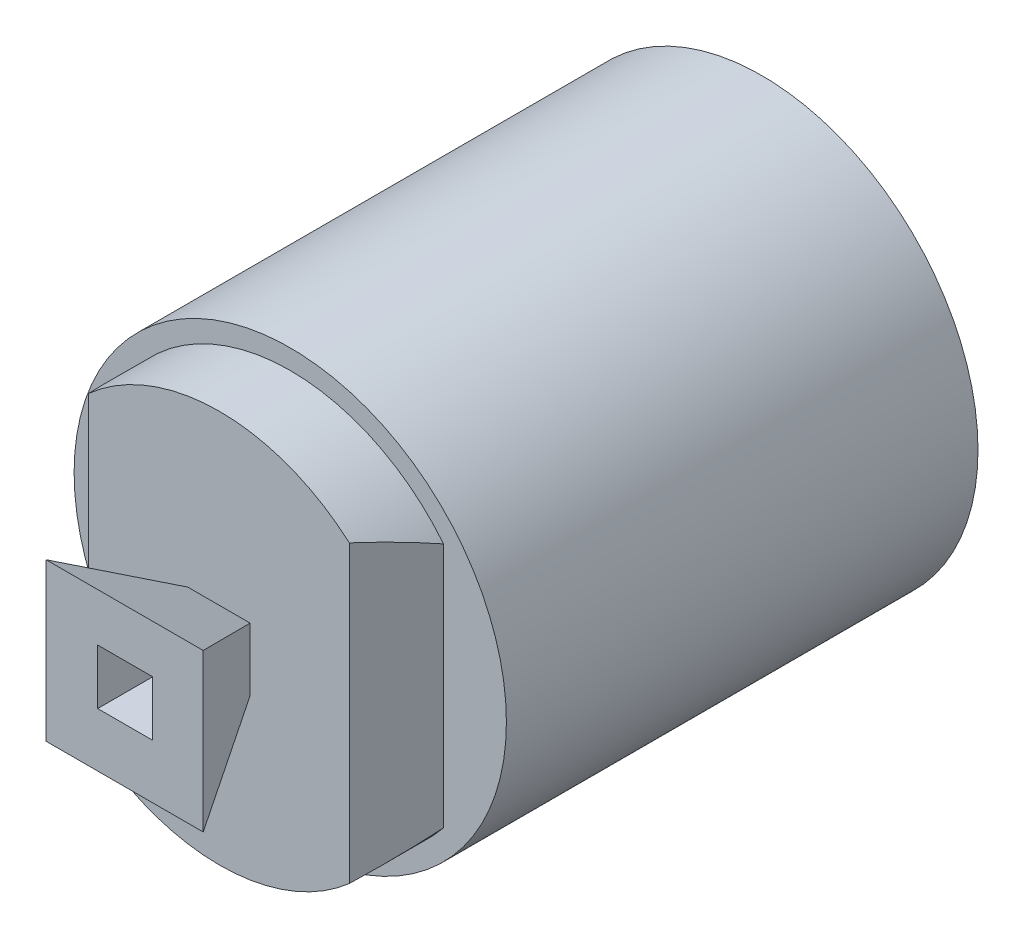
SolidWorks part; units mm, degrees
ref_plane "Plano frontal" through (0, 0, 0) normal (0, 0, 1) x (1, 0, 0)
ref_plane "Plano superior" through (0, 0, 0) normal (0, 1, 0) x (1, 0, 0)
ref_plane "Plano direito" through (0, 0, 0) normal (1, 0, 0) x (0, 0, -1)
sketch "Esboço2" plane through (0, 0, 0) normal (0, 0, 1) x (1, 0, 0)
  circle A0 centre (0, 0) radius 27.5
  dimension "D1" = 55
extrude "Ressalto-extrusão1" add sketch "Esboço2" along normal blind 60
sketch "Esboço3" plane through (0, 0, 0) normal (0, 0, 1) x (1, 0, 0)
  circle A0 centre (0, 0) radius 27
  dimension "D1" = 54
extrude "Corte-extrusão3" cut sketch "Esboço3" along normal blind 59 and the other way blind 2
sketch "Esboço4" plane through (0, 0, 0) normal (0, 0, 1) x (1, 0, 0)
  circle A0 centre (0, 0) radius 25
  point P0 (0, 0)
  dimension "D1" = 50
extrude "Ressalto-extrusão10" add sketch "Esboço4" along normal blind 69
sketch "Esboço6" plane through (0, 0, 0) normal (0, 1, 0) x (1, 0, 0)
  line L0 (-27.6679, -60) -> (-19.6679, -60)
  line L1 (-25, -60) -> (25, -60) construction
  line L2 (27.5, -60) -> (19.5, -60)
  line L3 (16.5157, -69) -> (19.5, -60)
  line L6 (-25, -69) -> (25, -69) construction
  line L9 (-16.6679, -69) -> (-19.6679, -60)
  line L10 (-27.6679, -60) -> (-27.6679, -69)
  line L11 (-27.6679, -69) -> (-16.6679, -69)
  line L12 (16.5157, -69) -> (27.5, -69)
  line L13 (27.5, -69) -> (27.5, -60)
extrude "Corte-extrusão4" cut sketch "Esboço6" against normal blind 48 and the other way blind 43
sketch "Esboço7" plane through (0, 0, 0) normal (0, 1, 0) x (1, 0, 0)
  line L0 (-4.0434, -69) -> (3.8912, -69)
  line L1 (-16.6679, -69) -> (16.5157, -69) construction
  line L3 (-10.0761, -81) -> (9.9239, -81)
  line L4 (-10.0761, -81) -> (-4.0434, -69)
  line L5 (9.9239, -81) -> (3.8912, -69)
  point P5 (-0.0761, -69)
  point P10 (-0.0761, -81)
extrude "Ressalto-extrusão11" add sketch "Esboço7" along normal blind 20 and the other way blind 20
sketch "Esboço9" plane through (0, 0, 0) normal (1, 0, 0) x (0, 0, -1)
  line L2 (-69, -18.7678) -> (-69, 18.7678) construction
  line L4 (-81, -20) -> (-81, 20) construction
  line L6 (-81, -10.3862) -> (-69, -4.3862)
  line L7 (-69, 3.6138) -> (-81, 9.6138)
  line L8 (-81, 9.6138) -> (-81, 21.387)
  line L9 (-81, 21.387) -> (-69, 21.387)
  line L10 (-69, 25) -> (-69, 18.6328) construction
  line L11 (-69, 21.387) -> (-69, 3.6138)
  line L12 (-69, -4.3862) -> (-69, -22.8068)
  line L13 (-69, -18.6328) -> (-69, -25) construction
  line L14 (-69, -22.8068) -> (-81, -22.8068)
  line L15 (-81, -22.8068) -> (-81, -10.3862)
  point P3 (-69, -0.3862)
  point P12 (-81, -0.3862)
extrude "Corte-extrusão5" cut sketch "Esboço9" against normal blind 24 and the other way blind 30
sketch "Esboço10" plane through (0, 0, 0) normal (0, 0, 1) x (1, 0, 0)
  circle A0 centre (0, 0) radius 25.8779
extrude "Corte-extrusão6" cut sketch "Esboço10" along normal blind 59
sketch "Esboço11" plane through (0, 0, 0) normal (0, 0, 1) x (1, 0, 0)
  line L1 (16, 18) -> (-16, 18)
  line L2 (16, 18) -> (16, -18)
  line L3 (16, -18) -> (-16, -18)
  line L4 (-16, 18) -> (-16, -18)
  line L5 (16, 18) -> (-16, -18) construction
  line L6 (16, -18) -> (-16, 18) construction
  point P0 (0, 0)
  dimension "D1" = 36
  dimension "D2" = 32
extrude "Corte-extrusão7" cut sketch "Esboço11" against normal blind 1 and the other way blind 68
sketch "Esboço12" plane through (0, 0, 0) normal (0, 1, 0) x (1, 0, 0)
  line L3 (-19.0697, -58.8178) -> (18.892, -58.8178)
  line L7 (-19.0697, -58.8178) -> (-15.9488, -68)
  line L8 (18.892, -58.8178) -> (15.8473, -68)
  line L9 (-15.9488, -68) -> (15.8473, -68)
  point P20 (-0.0507, -68)
extrude "Corte-extrusão10" cut sketch "Esboço12" against normal blind 15 and the other way blind 15
sketch "Esboço13" plane through (0, 0, 0) normal (0, 0, 1) x (1, 0, 0)
  line L1 (-3.5, 3.5) -> (3.5, 3.5)
  line L2 (-3.5, 3.5) -> (-3.5, -3.5)
  line L3 (-3.5, -3.5) -> (3.5, -3.5)
  line L4 (3.5, 3.5) -> (3.5, -3.5)
  line L5 (-3.5, 3.5) -> (3.5, -3.5) construction
  line L6 (-3.5, -3.5) -> (3.5, 3.5) construction
  point P0 (0, 0)
  dimension "D1" = 7
  dimension "D2" = 7
extrude "Corte-extrusão11" cut sketch "Esboço13" along normal blind 83
